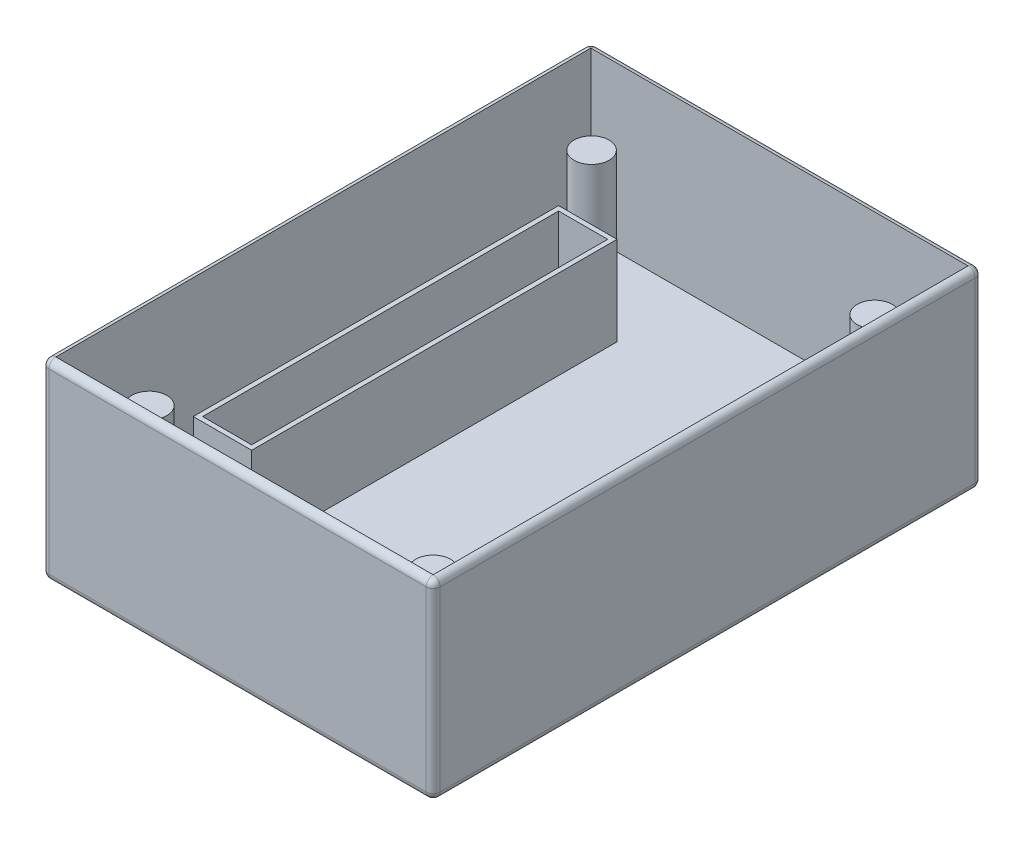
SolidWorks part; units mm, degrees
ref_plane "Front Plane" through (0, 0, 0) normal (0, 0, 1) x (1, 0, 0)
ref_plane "Top Plane" through (0, 0, 0) normal (0, 1, 0) x (1, 0, 0)
ref_plane "Right Plane" through (0, 0, 0) normal (1, 0, 0) x (0, 0, -1)
sketch "Sketch1" plane through (0, 0, 0) normal (0, 1, 0) x (1, 0, 0)
  line L0 (0, 0) -> (0, -23.5)
  line L1 (0, -23.5) -> (16.75, -23.5)
  line L2 (0, 0) -> (16.75, 0)
  line L3 (16.75, 0) -> (16.75, -23.5)
extrude "Boss-Extrude1" add sketch "Sketch1" along normal blind 1.2 contours L2 L3 L1 L0
sketch "Sketch3" plane through (0, 1.2, 0) normal (0, 1, 0) x (1, 0, 0)
  circle A0 centre (2.3, -2.2685) radius 0.75
  circle A1 centre (2.3, -21.2) radius 0.75
  circle A2 centre (14.45, -21.2) radius 0.75
  circle A3 centre (14.45, -2.3) radius 0.75
extrude "Boss-Extrude2" add sketch "Sketch3" along normal blind 5.2
sketch "Sketch5" plane through (0, 1.2, 0) normal (0, 1, 0) x (1, 0, 0)
  line L0 (0, 0) -> (16.75, 0)
  line L1 (16.75, 0) -> (16.75, -23.5)
  line L2 (16.75, -23.5) -> (0, -23.5)
  line L3 (0, -23.5) -> (0, 0)
  line L6 (0.3, -0.3) -> (16.45, -0.3)
  line L7 (16.45, -0.3) -> (16.45, -23.2)
  line L8 (16.45, -23.2) -> (0.3, -23.2)
  line L9 (0.3, -23.2) -> (0.3, -0.3)
extrude "Boss-Extrude3" add sketch "Sketch5" along normal blind 7
sketch "Sketch7" plane through (0, 1.2, 0) normal (0, 1, 0) x (1, 0, 0)
  line L0 (2.45, -3.63) -> (4.55, -3.63)
  line L1 (2.45, -3.63) -> (2.25, -3.63)
  line L2 (4.75, -3.63) -> (4.75, -19.27)
  line L3 (2.45, -19.07) -> (4.55, -19.07)
  line L4 (4.55, -19.07) -> (4.55, -3.83)
  line L5 (4.55, -3.83) -> (2.45, -3.83)
  line L6 (2.45, -3.83) -> (2.45, -19.07)
  line L7 (4.55, -3.63) -> (4.75, -3.63)
  line L8 (4.75, -19.27) -> (2.25, -19.27)
  line L9 (2.25, -3.63) -> (2.25, -19.27)
  point P0 (0, 0)
  dimension "D1" = 2.5
  dimension "D2" = 15.24
extrude "Boss-Extrude5" add sketch "Sketch7" along normal blind 3.8
fillet "Fillet4" radius 0.3 12 edges at (0, 8.2, 11.75) (8.375, 8.2, 0) (0, 4.1, 0) (16.75, 8.2, 11.75) (16.75, 4.1, 0) (0, 4.1, 23.5) (8.375, 8.2, 23.5) (16.75, 4.1, 23.5) (8.375, 0, 23.5) (16.75, 0, 11.75) (8.375, 0, 0) (0, 0, 11.75)
